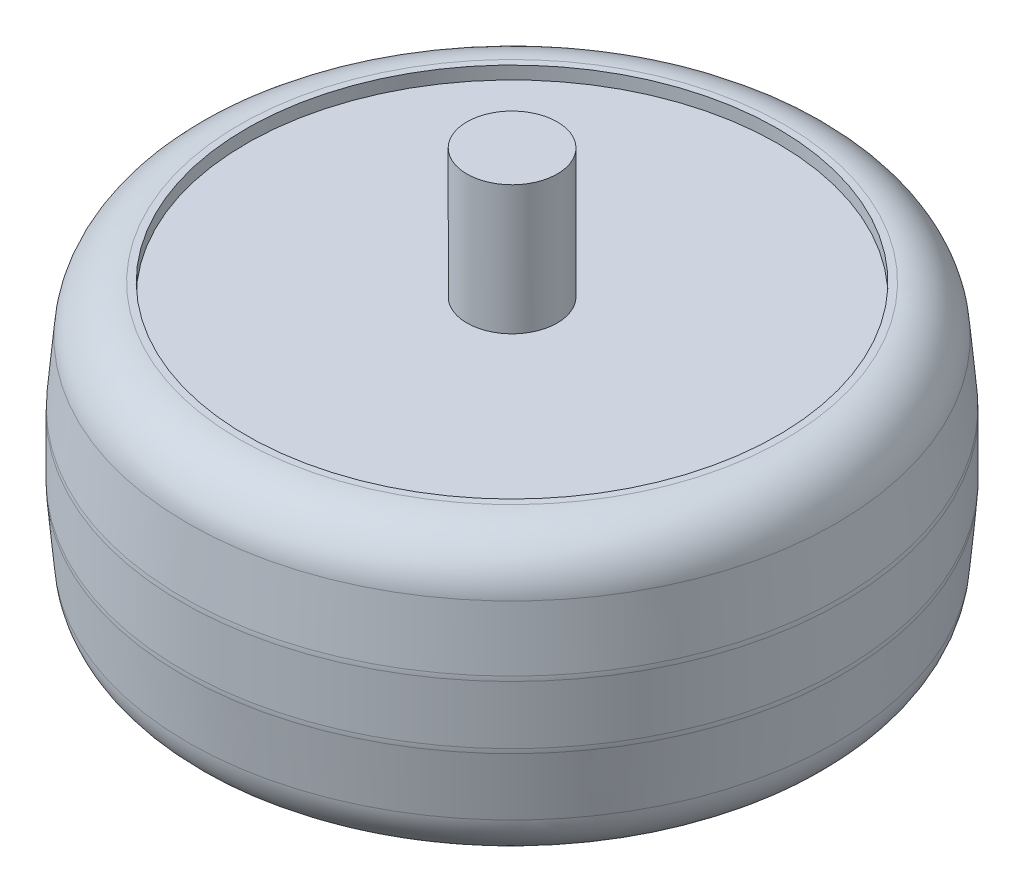
SolidWorks part; units mm, degrees
ref_plane "Front Plane" through (0, 0, 0) normal (0, 0, 1) x (1, 0, 0)
ref_plane "Top Plane" through (0, 0, 0) normal (0, 1, 0) x (1, 0, 0)
ref_plane "Right Plane" through (0, 0, 0) normal (1, 0, 0) x (0, 0, -1)
sketch "Sketch1" plane through (0, 0, 0) normal (0, 1, 0) x (1, 0, 0)
  circle A0 centre (0, 0) radius 25.5
  dimension "D1" = 51
extrude "Boss-Extrude1" add sketch "Sketch1" along normal blind 20
sketch "Sketch2" plane through (0, 0, 0) normal (0, -1, 0) x (1, 0, 0)
  circle A0 centre (0, 0) radius 3.5
  dimension "D1" = 7
extrude "Boss-Extrude2" add sketch "Sketch2" along normal blind 10 and the other way blind 30
sketch "Sketch3" plane through (0, 0, 0) normal (0, 1, 0) x (1, 0, 0)
  circle A0 centre (0, 0) radius 25.534
  circle A1 centre (0, 0) radius 20.5903
extrude "Boss-Extrude3" add sketch "Sketch3" against normal blind 1 and the other way blind 21
chamfer "Chamfer1" distance 0.75 angle 85 1 edges at (0, -1, 25.534) first distance on face at (0, -1, 20.5903)
chamfer "Chamfer2" distance 0.75 angle 85 1 edges at (0, 21, 25.534) first distance on face at (0, 21, 25.534)
fillet "Fillet1" radius 4 4 edges at (0, 21, 24.784) (0, 12.4275, 25.534) (0, 7.5725, 25.534) (0, -1, 24.784)
